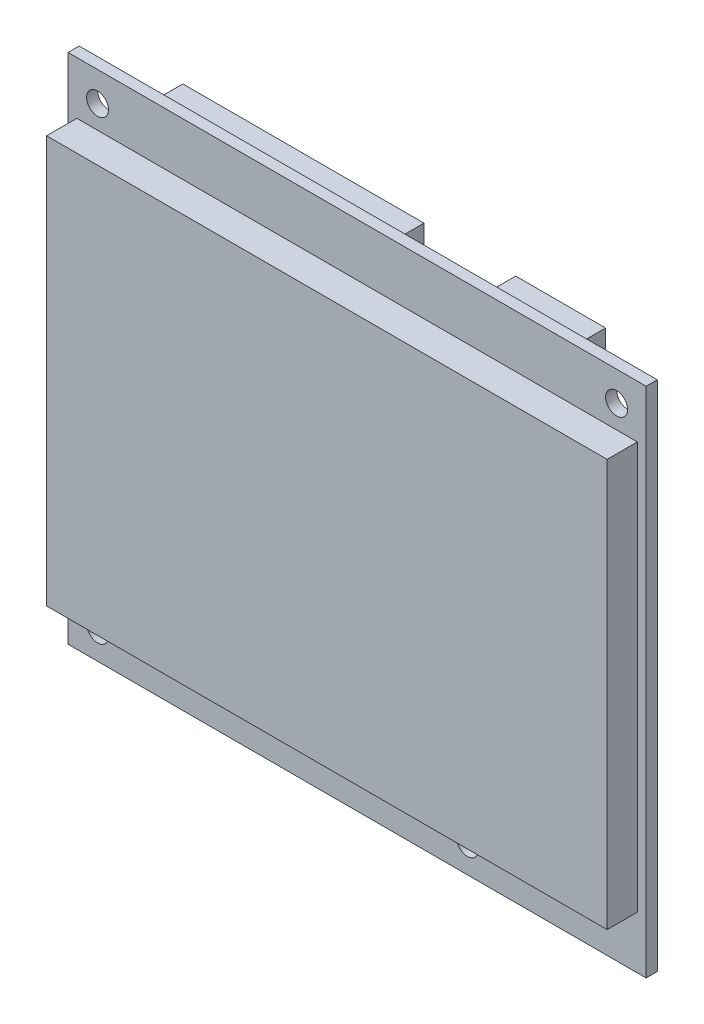
SolidWorks part; units mm, degrees
ref_plane "Front Plane" through (0, 0, 0) normal (0, 0, 1) x (1, 0, 0)
ref_plane "Top Plane" through (0, 0, 0) normal (0, 1, 0) x (1, 0, 0)
ref_plane "Right Plane" through (0, 0, 0) normal (1, 0, 0) x (0, 0, -1)
sketch "Sketch1" plane through (0, 0, 0) normal (0, 0, -1) x (-1, 0, 0)
  line L0 (42.4, 0) -> (43.6432, 0) construction
  line L1 (-32.4, -24.3) -> (32.4, -24.3) construction
  line L2 (-32.4, -24.3) -> (-32.4, 24.3) construction
  line L3 (-32.4, 24.3) -> (32.4, 24.3) construction
  line L4 (32.4, -24.3) -> (32.4, 24.3) construction
  line L5 (-32.4, -24.3) -> (32.4, 24.3) construction
  line L6 (-32.4, 24.3) -> (32.4, -24.3) construction
  line L7 (-36.8, 28.77) -> (42.4, 28.77) construction
  line L8 (-36.8, 28.77) -> (-36.8, -28.77) construction
  line L9 (-36.8, -28.77) -> (42.4, -28.77) construction
  line L10 (42.4, 28.77) -> (42.4, -28.77) construction
  line L11 (-38.0432, 36.2077) -> (43.6432, 36.2077)
  line L12 (-38.0432, 36.2077) -> (-38.0432, -36.2077)
  line L13 (-38.0432, -36.2077) -> (43.6432, -36.2077)
  line L14 (43.6432, 36.2077) -> (43.6432, -36.2077)
  line L15 (-36.8, 0) -> (-38.0432, 0) construction
  line L16 (2.8, -28.77) -> (2.8, -36.2077) construction
  line L17 (2.8, 28.77) -> (2.8, 36.2077) construction
  point P0 (0, 0)
  dimension "D1" = 64.8
  dimension "D2" = 48.6
  dimension "D3" = 4.4
  dimension "D4" = 4.47
  dimension "D5" = 57.54
  dimension "D6" = 79.2
  dimension "D8" = 72.4154
  dimension "D9" = 81.6864
extrude "Boss-Extrude1" add sketch "Sketch1" along normal blind 1.5748
sketch "Sketch2" plane through (0, 0, 0) normal (0, 0, -1) x (-1, 0, 0)
  line L1 (-36.8, -28.77) -> (42.4, -28.77)
  line L2 (-36.8, -28.77) -> (-36.8, 28.77)
  line L3 (-36.8, 28.77) -> (42.4, 28.77)
  line L4 (42.4, -28.77) -> (42.4, 28.77)
  line L10 (-32.4, -24.3) -> (32.4, -24.3) construction
  line L11 (-32.4, -24.3) -> (-32.4, 24.3) construction
  line L12 (-32.4, 24.3) -> (32.4, 24.3) construction
  line L13 (32.4, -24.3) -> (32.4, 24.3) construction
  line L14 (-32.4, -24.3) -> (32.4, 24.3) construction
  line L15 (-32.4, 24.3) -> (32.4, -24.3) construction
  point P0 (0, 0)
  point P14 (0, 0)
  dimension "D1" = 57.54
  dimension "D2" = 79.2
  dimension "D3" = 4.4
  dimension "D4" = 48.6
  dimension "D5" = 64.8
  dimension "D6" = 4.47
extrude "Boss-Extrude2" add sketch "Sketch2" against normal blind 4.27
sketch "Sketch3" plane through (0, 0, -1.5748) normal (0, 0, 1) x (1, 0, 0)
  line L1 (25.66, 33.8141) -> (12.96, 33.8141)
  line L2 (25.66, 33.8141) -> (25.66, 28.7341)
  line L3 (25.66, 28.7341) -> (12.96, 28.7341)
  line L4 (12.96, 33.8141) -> (12.96, 28.7341)
  line L6 (0, 33.8141) -> (-34.0711, 33.8141)
  line L7 (0, 33.8141) -> (0, 28.7341)
  line L8 (0, 28.7341) -> (-34.0711, 28.7341)
  line L9 (-34.0711, 33.8141) -> (-34.0711, 28.7341)
  line L10 (-34.0711, -29.1593) -> (0, -29.1593)
  line L11 (-34.0711, -29.1593) -> (-34.0711, -34.2393)
  line L12 (-34.0711, -34.2393) -> (0, -34.2393)
  line L13 (0, -29.1593) -> (0, -34.2393)
  dimension "D1" = 5.08
  dimension "D2" = 12.7
sketch "Sketch4" plane through (0, 0, -1.5748) normal (0, 0, -1) x (-1, 0, 0)
  line L0 (43.6432, 36.2077) -> (-38.0432, 36.2077) construction
  line L1 (-38.0432, 36.2077) -> (-38.0432, -36.2077) construction
  line L2 (43.6432, -36.2077) -> (43.6432, 36.2077) construction
  line L3 (-38.0432, -36.2077) -> (43.6432, -36.2077) construction
  circle A0 centre (39.4682, 32.0327) radius 1.55
  circle A1 centre (39.4682, -32.4077) radius 1.55
  circle A2 centre (-12.7918, -32.4077) radius 1.55
  circle A3 centre (-33.8682, 32.0327) radius 1.55
  dimension "D3" = 3.1
  dimension "D1" = 4.175
  dimension "D2" = 4.175
  dimension "D4" = 4.175
  dimension "D5" = 3.8
  dimension "D6" = 52.26
extrude "Cut-Extrude1" cut sketch "Sketch4" against normal through all
extrude "Boss-Extrude3" add sketch "Sketch3" against normal blind 5.08
sketch "Sketch5" plane through (0, 0, -1.5748) normal (0, 0, -1) x (-1, 0, 0)
  line L0 (19.4766, 13.5356) -> (30.7313, 2.2809)
  line L1 (30.7313, 2.2809) -> (19.4766, -8.9738)
  line L2 (19.4766, -8.9738) -> (8.2218, 2.2809)
  line L3 (8.2218, 2.2809) -> (19.4766, 13.5356)
  line L5 (-15.8477, -24.7973) -> (-26.991, -24.7973)
  line L6 (-15.8477, -24.7973) -> (-15.8477, -9.9767)
  line L7 (-15.8477, -9.9767) -> (-26.991, -9.9767)
  line L8 (-26.991, -24.7973) -> (-26.991, -9.9767)
  line L9 (-37.0611, -34.1253) -> (-31.3584, -34.1253)
  line L10 (-37.0611, -34.1253) -> (-37.0611, -35.0607)
  line L11 (-37.0611, -35.0607) -> (-31.3584, -35.0607)
  line L12 (-31.3584, -34.1253) -> (-31.3584, -35.0607)
extrude "Boss-Extrude4" add sketch "Sketch5" along normal blind 1
